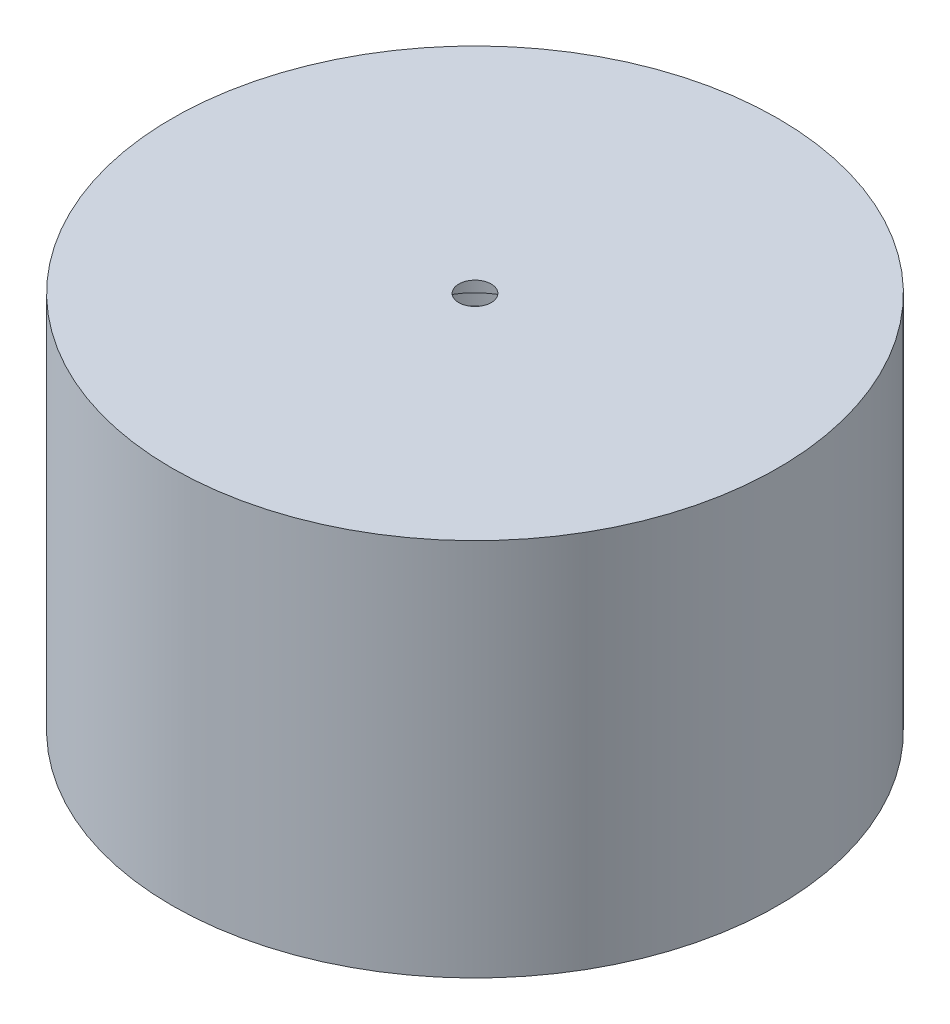
SolidWorks part; units mm, degrees
ref_plane "Спереди" through (0, 0, 0) normal (0, 0, 1) x (1, 0, 0)
ref_plane "Сверху" through (0, 0, 0) normal (0, 1, 0) x (1, 0, 0)
ref_plane "Справа" through (0, 0, 0) normal (1, 0, 0) x (0, 0, -1)
sketch "Эскиз1" plane through (0, 0, 0) normal (0, 0, 1) x (1, 0, 0)
  line L0 (0, 0) -> (0, 60) construction
  line L1 (17, 27) -> (17, 25.8)
  line L6 (8, 56.5) -> (9.5181, 56.5)
  line L7 (9.5181, 56.5) -> (9.5181, 54)
  line L8 (9.5181, 54) -> (8, 54)
  line L10 (8, 58.6338) -> (8, 56.5)
  line L11 (8, 54) -> (8, 52)
  line L12 (8, 52) -> (12, 47)
  line L13 (12, 47) -> (12, 45)
  line L14 (12, 45) -> (13.9013, 45)
  line L15 (13.9013, 45) -> (13.9013, 42.5)
  line L16 (13.9013, 42.5) -> (12, 42.5)
  line L17 (12, 39.5) -> (9.0242, 39.5) construction
  line L18 (12, 42.5) -> (12, 41)
  line L19 (12, 36.5) -> (12, 38)
  line L20 (12, 34) -> (13.9013, 34)
  line L21 (13.9013, 34) -> (13.9013, 36.5)
  line L22 (13.9013, 36.5) -> (12, 36.5)
  line L23 (12, 34) -> (12, 32)
  line L24 (12, 32) -> (17, 27)
  line L29 (17, 25.8) -> (30, 25.8)
  line L33 (30, 25.8) -> (30, 23.3)
  line L34 (30, 23.3) -> (28.4, 23.3)
  line L35 (28.4, 23.3) -> (28.4, 15.3)
  line L37 (8, 58.6338) -> (2, 62.0979)
  line L38 (2, 62.0979) -> (37.4277, 62.0979)
  line L40 (28.4, 15.3) -> (37.4277, 15.3)
  line L41 (37.4277, 15.3) -> (37.4277, 62.0979)
  arc A2 (12, 38) -> (12, 41) centre (12, 39.5) ccw
  point P22 (12, 41)
  dimension "D5" = 2.5
  dimension "D7" = 1.5
  dimension "D4" = 16
  dimension "D6" = 2
  dimension "D9" = 24
  dimension "D10" = 5
  dimension "D11" = 2.5
  dimension "D13" = 2
  dimension "D15" = 1.5
  dimension "D16" = 2
  dimension "D17" = 5
  dimension "D18" = 34
  dimension "D19" = 1.2
  dimension "D20" = 2.5
  dimension "D21" = 8
  dimension "D22" = 13
  dimension "D23" = 1.6
revolve "Повернуть1" add sketch "Эскиз1" angle 360 about L0 reverse direction yes
